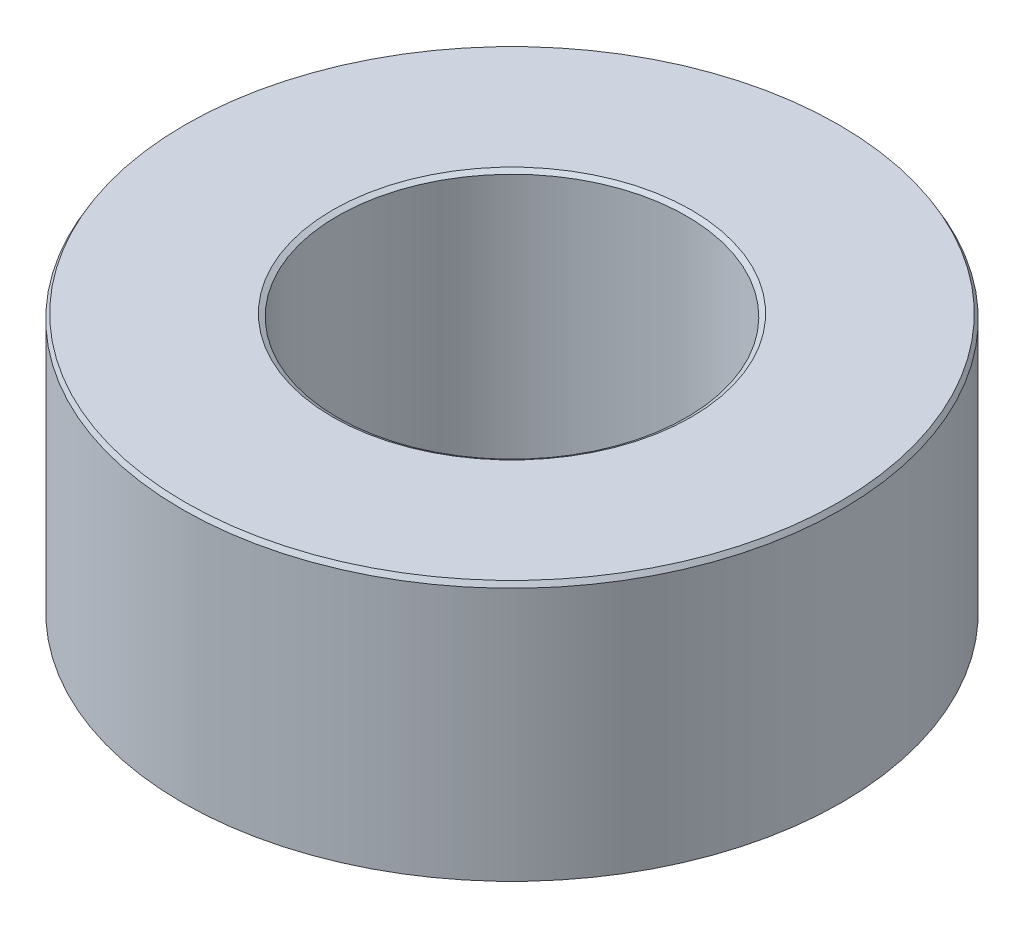
SolidWorks part; units mm, degrees
ref_plane "Front Plane" through (0, 0, 0) normal (0, 0, 1) x (1, 0, 0)
ref_plane "Top Plane" through (0, 0, 0) normal (0, 1, 0) x (1, 0, 0)
ref_plane "Right Plane" through (0, 0, 0) normal (1, 0, 0) x (0, 0, -1)
sketch "Sketch1" plane through (0, 0, 0) normal (0, 1, 0) x (1, 0, 0)
  circle A0 centre (0, 0) radius 50
  dimension "SLEEVE_OD" = 100
extrude "Boss-Extrude1" add sketch "Sketch1" along normal blind 39.6511
sketch "Sketch2" plane through (0, 0, 0) normal (0, 1, 0) x (1, 0, 0)
  circle A0 centre (0, 0) radius 26.4679
  dimension "BORE_D" = 52.9358
extrude "Cut-Extrude1" cut sketch "Sketch2" along normal through all
chamfer "Chamfer1" distance 0.7321 angle 30 4 edges at (0, 39.6511, 26.4679) (0, 0, 26.4679) (0, 0, 50) (0, 39.6511, 50) first distance on face at (0, 39.6511, 26.4679) first distance on face at (0, 0, 26.4679) first distance on face at (0, 39.6511, 50)
